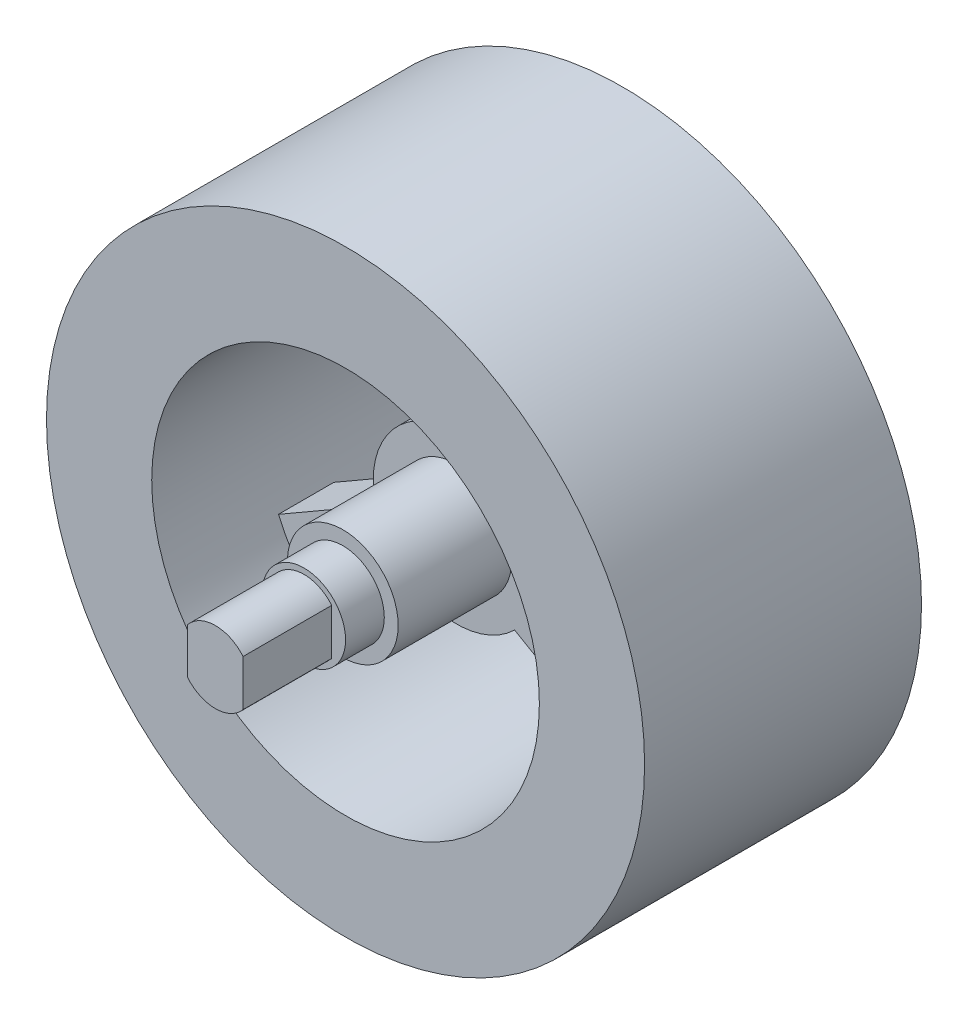
SolidWorks part; units mm, degrees
ref_plane "Front Plane" through (0, 0, 0) normal (0, 0, 1) x (1, 0, 0)
ref_plane "Top Plane" through (0, 0, 0) normal (0, 1, 0) x (1, 0, 0)
ref_plane "Right Plane" through (0, 0, 0) normal (1, 0, 0) x (0, 0, -1)
sketch "Sketch1" plane through (0, 0, 0) normal (0, 0, 1) x (1, 0, 0)
  circle A0 centre (0, 0) radius 7.5
  dimension "D1" = 15
extrude "Boss-Extrude1" add sketch "Sketch1" along normal mid plane 65 contours A0
sketch "Sketch3" plane through (0, 0, 0) normal (0, 0, 1) x (1, 0, 0)
  circle A0 centre (0, 0) radius 6.5
  dimension "D1" = 13
extrude "Boss-Extrude3" add sketch "Sketch3" along normal mid plane 97
sketch "Sketch4" plane through (0, 0, 0) normal (0, 0, 1) x (1, 0, 0)
  circle A0 centre (0, 0) radius 54
  circle A1 centre (0, 0) radius 35
  dimension "D1" = 108
  dimension "D2" = 70
extrude "Boss-Extrude4" add sketch "Sketch4" along normal mid plane 50
sketch "Sketch5" plane through (0, 0, 0) normal (0, 0, 1) x (1, 0, 0)
  line L0 (14.52, -3.7643) -> (10.52, -10.6925)
  line L1 (-4, 14.4568) -> (4, 14.4568)
  line L2 (-4, 14.4568) -> (-4, 35)
  line L3 (-4, 35) -> (4, 35)
  line L4 (4, 14.4568) -> (4, 35)
  line L5 (14.52, -3.7643) -> (32.3109, -14.0359)
  line L6 (32.3109, -14.0359) -> (28.3109, -20.9641)
  line L7 (10.52, -10.6925) -> (28.3109, -20.9641)
  line L8 (-10.52, -10.6925) -> (-14.52, -3.7643)
  line L9 (-10.52, -10.6925) -> (-28.3109, -20.9641)
  line L10 (-28.3109, -20.9641) -> (-32.3109, -14.0359)
  line L11 (-14.52, -3.7643) -> (-32.3109, -14.0359)
  line L12 (0, 0) -> (4, 14.4568) construction
  circle A0 centre (0, 0) radius 15
  circle A1 centre (0, 0) radius 35 construction
  dimension "D1" = 30
  dimension "D2" = 8
  dimension "D3" = 3
extrude "Boss-Extrude5" add sketch "Sketch5" along normal mid plane 10 contours L1 A0 L8 L0 | A0 L4 L3 L2 | A0 L7 L6 L5 | A0 L11 L10 L9 | L8 A0 | L0 A0 | L1 A0 | L2 L1 L4 L3 region at (12.7084, -7.3372, 0) region at (21.5723, -12.4547, 0) region at (0, 0, 0) region at (-12.7084, -7.3372, 0) region at (-21.5723, -12.4547, 0) region at (0, 24.9095, 0) region at (0, 14.6744, 0)
sketch "Sketch6" plane through (0, 0, 0) normal (0, 0, 1) x (1, 0, 0)
  circle A0 centre (0, 0) radius 10
  dimension "D1" = 20
extrude "Boss-Extrude6" add sketch "Sketch6" along normal mid plane 51
sketch "Sketch7" plane through (0, 0, -48.5) normal (0, 0, -1) x (-1, 0, 0)
  line L1 (5, 4.1533) -> (6.5, 4.1533)
  line L2 (5, 4.1533) -> (5, -4.1533)
  line L3 (5, -4.1533) -> (6.5, -4.1533)
  line L4 (6.5, 4.1533) -> (6.5, -4.1533)
  line L5 (-5, 4.1533) -> (-6.5, 4.1533)
  line L6 (-5, 4.1533) -> (-5, -4.1533)
  line L7 (-5, -4.1533) -> (-6.5, -4.1533)
  line L8 (-6.5, 4.1533) -> (-6.5, -4.1533)
  circle A0 centre (0, 0) radius 6.5 construction
  circle A1 centre (0, 0) radius 6.5 construction
  dimension "D1" = 10
extrude "Cut-Extrude1" cut sketch "Sketch7" against normal blind 16
mirror "Mirror1" about plane through (0, 0, 0) normal (0, 0, 1) of "Cut-Extrude1"
sketch "Sketch8" plane through (0, 0, -48.5) normal (0, 0, -1) x (-1, 0, 0)
  circle A0 centre (0, 0) radius 3
  dimension "D1" = 6
extrude "Cut-Extrude2" cut sketch "Sketch8" against normal up to surface (48.5 mm away) up to plane "Front Plane"
